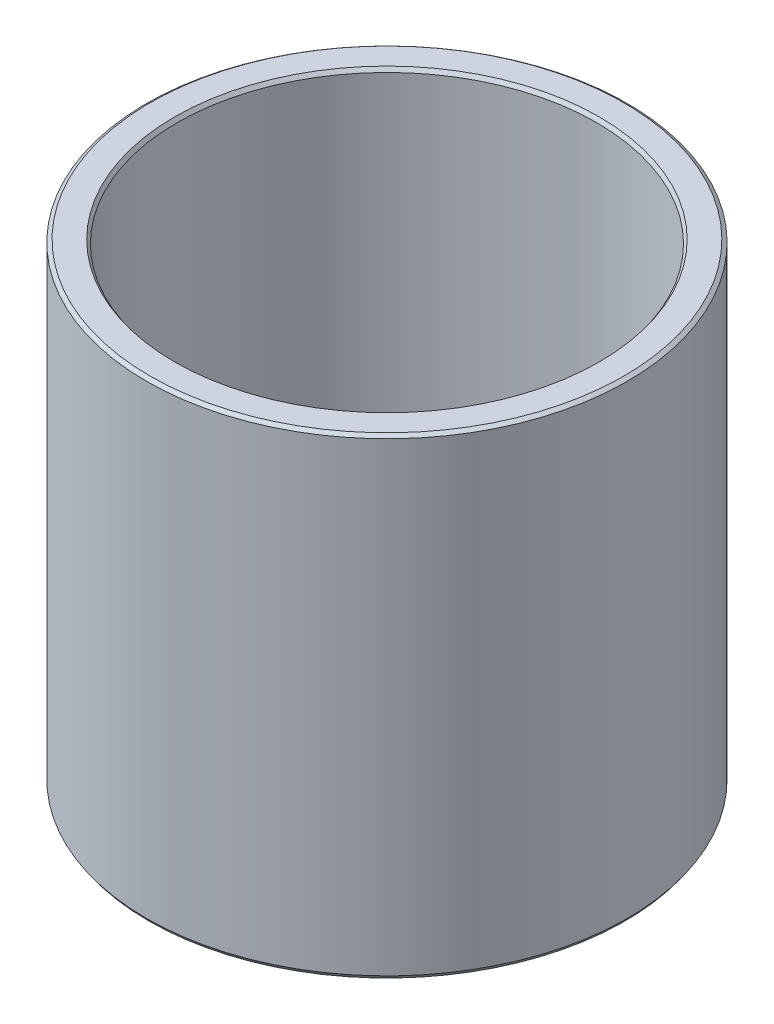
SolidWorks part; units mm, degrees
ref_plane "Front Plane" through (0, 0, 0) normal (0, 0, 1) x (1, 0, 0)
ref_plane "Top Plane" through (0, 0, 0) normal (0, 1, 0) x (1, 0, 0)
ref_plane "Right Plane" through (0, 0, 0) normal (1, 0, 0) x (0, 0, -1)
sketch "Sketch1" plane through (0, 0, 0) normal (0, 1, 0) x (1, 0, 0)
  circle A0 centre (0, 0) radius 55
  dimension "SLEEVE_OD" = 110
extrude "Boss-Extrude1" add sketch "Sketch1" along normal blind 107.8067
sketch "Sketch2" plane through (0, 0, 0) normal (0, 1, 0) x (1, 0, 0)
  circle A0 centre (0, 0) radius 47.9541
  dimension "BORE_D" = 95.9083
extrude "Cut-Extrude1" cut sketch "Sketch2" along normal through all
chamfer "Chamfer1" distance 0.591 angle 55.061 4 edges at (0, 107.8067, 47.9541) (0, 0, 47.9541) (0, 0, 55) (0, 107.8067, 55) first distance on face at (0, 107.8067, 47.9541) first distance on face at (0, 0, 47.9541) first distance on face at (0, 107.8067, 55)
